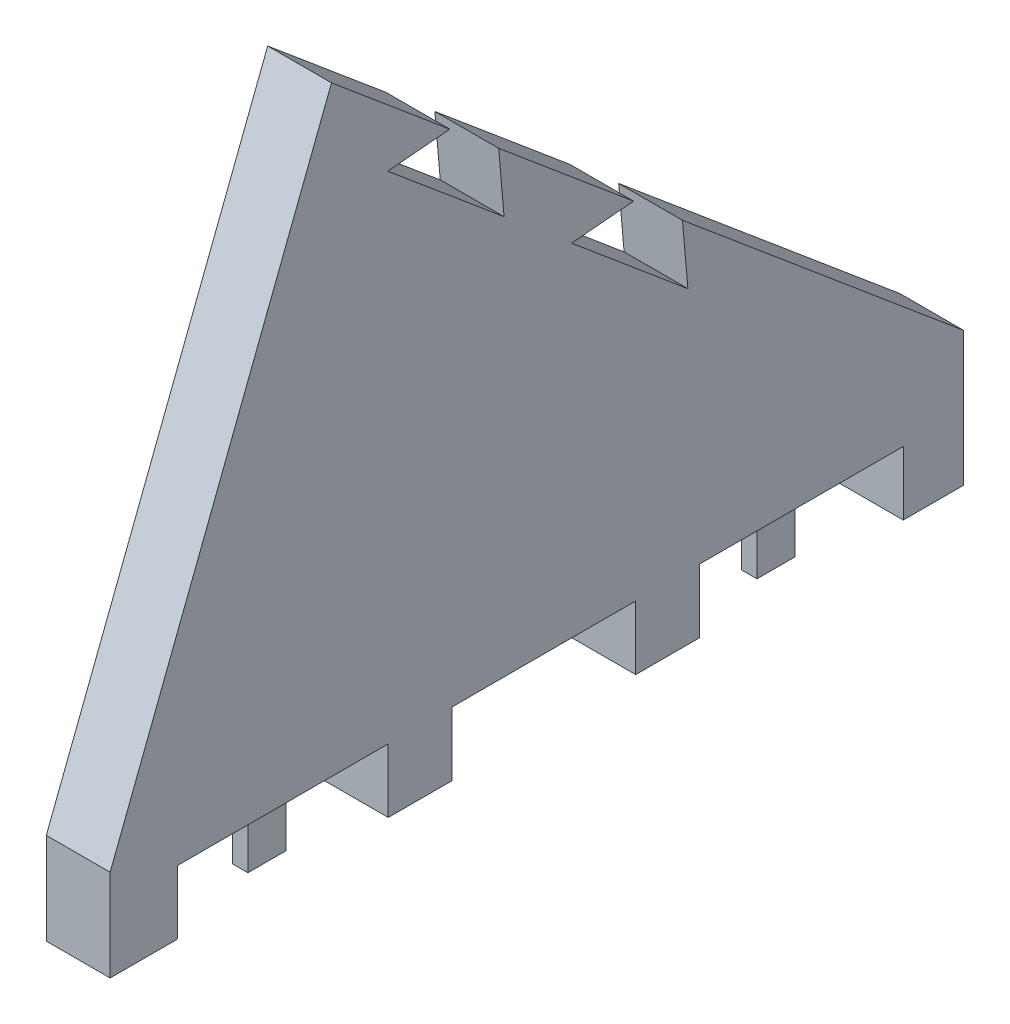
SolidWorks part; units mm, degrees
material "PVC 0.007 Plasticized"
ref_plane "Front Plane" through (0, 0, 0) normal (0, 0, 1) x (1, 0, 0)
ref_plane "Top Plane" through (0, 0, 0) normal (0, 1, 0) x (1, 0, 0)
ref_plane "Right Plane" through (0, 0, 0) normal (1, 0, 0) x (0, 0, -1)
sketch "Sketch2" plane through (0, 0, 0) normal (1, 0, 0) x (0, 0, -1)
  line L0 (12.1929, 0) -> (7.1929, 0)
  line L1 (-7.1929, 5) -> (7.1929, 5)
  line L3 (-12.1929, 0) -> (-12.1929, 4.9988)
  line L4 (-12.1929, 4.9988) -> (-18.4429, 4.9988)
  line L6 (18.4429, -0.0012) -> (21.4429, -0.0012)
  line L7 (12.1929, 0) -> (12.1929, 4.9988)
  line L8 (12.1929, 4.9988) -> (18.4429, 4.9988)
  line L10 (-12.1929, 0) -> (-7.1929, 0)
  line L13 (-7.1929, 0) -> (-7.1929, 5)
  line L17 (7.1929, 5) -> (7.1929, 0)
  line L18 (0, 55) -> (0, -55) construction
  line L19 (-28.6919, 0.0051) -> (-32.8929, 0.0051)
  line L23 (-18.4429, -0.0012) -> (-21.4429, -0.0012)
  line L24 (-18.4429, -0.0012) -> (-18.4429, 4.9988)
  line L26 (-21.4429, -0.0012) -> (-21.4429, 4.9988)
  line L27 (17.6467, 23.3025) -> (32.8929, 10.5095)
  line L28 (28.1589, 0.0051) -> (32.8929, 0.0051)
  line L29 (-3.5419, 41.0818) -> (7.0296, 32.2113)
  line L30 (21.4429, -0.0012) -> (21.4429, 4.9988)
  line L31 (18.4429, 4.9988) -> (21.4429, 4.9988)
  line L32 (18.4429, -0.0012) -> (18.4429, 4.9988)
  line L33 (21.4429, 4.9988) -> (27.8929, 4.9988)
  line L34 (-18.4429, 4.9988) -> (-21.4429, 4.9988)
  line L35 (-21.4429, 4.9988) -> (-27.8929, 4.9988)
  line L36 (2.1747, 31.7866) -> (7.0296, 32.2113)
  line L38 (32.8929, 0.0051) -> (32.8929, 10.5095)
  line L41 (-32.8929, 10.0051) -> (-16.6385, 52.0712)
  line L42 (-16.6385, 52.0712) -> (-7.3721, 44.2957)
  line L43 (10.8598, 28.9974) -> (14.567, 25.8866)
  line L44 (-7.3721, 44.2957) -> (-12.227, 43.871)
  line L45 (-12.227, 43.871) -> (-3.1171, 36.2269)
  line L46 (-3.1171, 36.2269) -> (-3.5419, 41.0818)
  line L47 (11.2845, 24.1425) -> (2.1747, 31.7866)
  line L51 (10.8598, 28.9974) -> (11.2845, 24.1425)
  line L52 (-32.8929, 10.0051) -> (-33.9836, 7.1822)
  line L54 (-33.9836, 7.1822) -> (-499959.4784, 33.9632)
  line L55 (14.567, 25.8866) -> (17.6467, 23.3025)
  line L56 (-33.9836, 7.1822) -> (-33.9836, 0.0051)
  line L57 (-33.9836, 0.0051) -> (-32.8929, 0.0051)
  line L58 (1.7438, 36.6466) -> (10.374, 46.9315) construction
  line L59 (-27.8929, 4.9988) -> (-28.6919, 4.9988)
  line L60 (-28.6919, 4.9988) -> (-28.6919, 0.0051)
  line L61 (27.8929, 4.9988) -> (28.1589, 4.9988)
  line L62 (28.1589, 4.9988) -> (28.1589, 0.0051)
  point P4 (0, 0)
  point P17 (-20.3929, 5)
  point P30 (0, 0)
  dimension "D2" = 15.7
  dimension "D3" = 130
  dimension "D4" = 5
  dimension "D5" = 0
  dimension "D6" = 45
  dimension "D7" = 5
  dimension "D10" = 3
  dimension "D11" = 5
  dimension "D12" = 45
  dimension "D13" = 5
  dimension "D14" = 4.8734
  dimension "D18" = 5
  dimension "D19" = 6.9
extrude "Boss-Extrude2" add sketch "Sketch2" along normal blind 5 contours L29 L46 L45 L44 L42 L41 L35 L26 L23 L24 L4 L3 L10 L13 L1 L17 L0 L7 L8 L32 L6 L30 L33 L28 L38 L27 | L19 region at (0, 19.3365, 4.367)
extrude "Boss-Extrude3" add sketch "Sketch2<4>" along normal blind 1.2 from offset 2.05 contours L32 L6 L30 L31 | L24 L34 L26 L23 region at (0, 2.4988, -19.9429) region at (0, 2.4988, 19.9429)
sketch "Sketch2<4>" plane through (0, 0, 0) normal (1, 0, 0) x (0, 0, -1) same geometry as "Sketch2"
